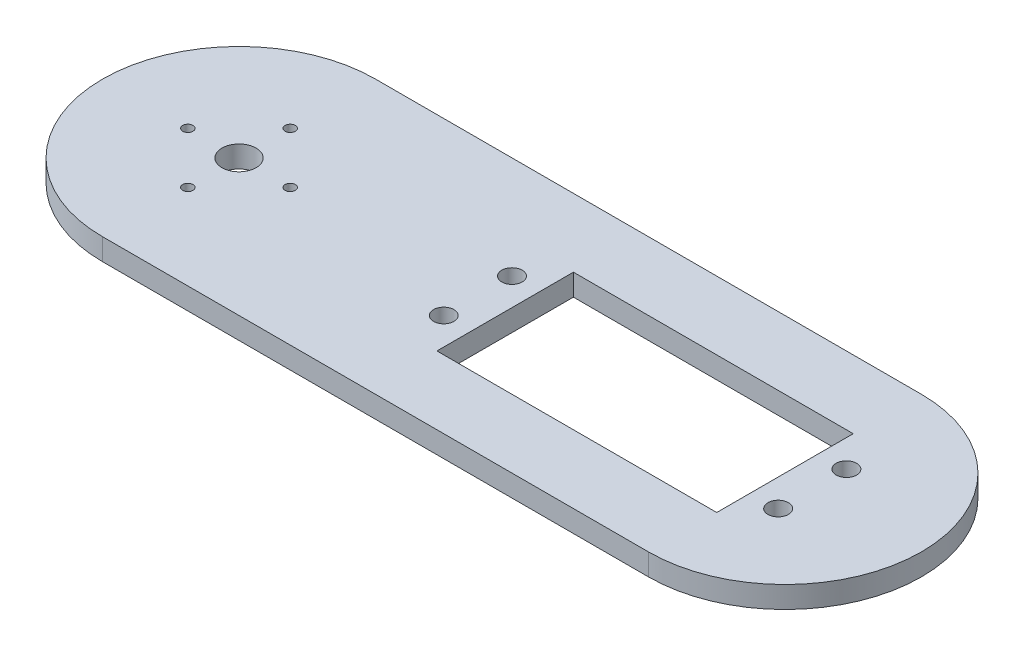
SolidWorks part; units mm, degrees
material "Pine"
ref_plane "Front Plane" through (0, 0, 0) normal (0, 0, 1) x (1, 0, 0)
ref_plane "Top Plane" through (0, 0, 0) normal (0, 1, 0) x (1, 0, 0)
ref_plane "Right Plane" through (0, 0, 0) normal (1, 0, 0) x (0, 0, -1)
sketch "Sketch3" plane through (0, 0, 0) normal (0, 1, 0) x (1, 0, 0)
  line L0 (-40.3723, 0) -> (39.6277, 0) construction
  line L1 (-40.3723, 20) -> (39.6277, 20)
  line L2 (-40.3723, -20) -> (39.6277, -20)
  line L4 (39.6277, 10) -> (-1.3723, 10)
  line L5 (39.6277, 10) -> (39.6277, -10)
  line L6 (39.6277, -10) -> (-1.3723, -10)
  line L7 (-1.3723, 10) -> (-1.3723, -10)
  arc A0 (-40.3723, 20) -> (-40.3723, -20) centre (-40.3723, 0) ccw
  arc A1 (39.6277, -20) -> (39.6277, 20) centre (39.6277, 0) ccw
  circle A2 centre (-40.3723, 0) radius 2.5
  circle A3 centre (-32.8723, 0) radius 0.75
  circle A4 centre (-5.3723, 5) radius 1.5
  circle A5 centre (-5.3723, -5) radius 1.5
  circle A6 centre (43.6277, 5) radius 1.5
  circle A7 centre (43.6277, -5) radius 1.5
  circle A8 centre (-47.8723, 0) radius 0.75
  circle A9 centre (-40.3723, 7.5) radius 0.75
  circle A10 centre (-40.3723, -7.5) radius 0.75
  point P3 (-0.3723, 0)
  dimension "D1" = 20
  dimension "D7" = 5
  dimension "D9" = 1.5
  dimension "D11" = 1.5
  dimension "D14" = 1.5
  dimension "D15" = 1.5
  dimension "D26" = 3
  dimension "D27" = 3
  dimension "D28" = 3
  dimension "D29" = 3
  dimension "D2" = 80
  dimension "D3" = 0
  dimension "D4" = 20
  dimension "D5" = 10
  dimension "D6" = 41
  dimension "D8" = 20
  dimension "D10" = 7.5
  dimension "D12" = 7.5
  dimension "D13" = 7.5
  dimension "D16" = 7.5
  dimension "D18" = 5
  dimension "D19" = 5
  dimension "D20" = 5
  dimension "D21" = 5
  dimension "D22" = 4
  dimension "D23" = 4
  dimension "D24" = 4
  dimension "D25" = 4
extrude "Boss-Extrude1" add sketch "Sketch3" along normal blind 3.175
